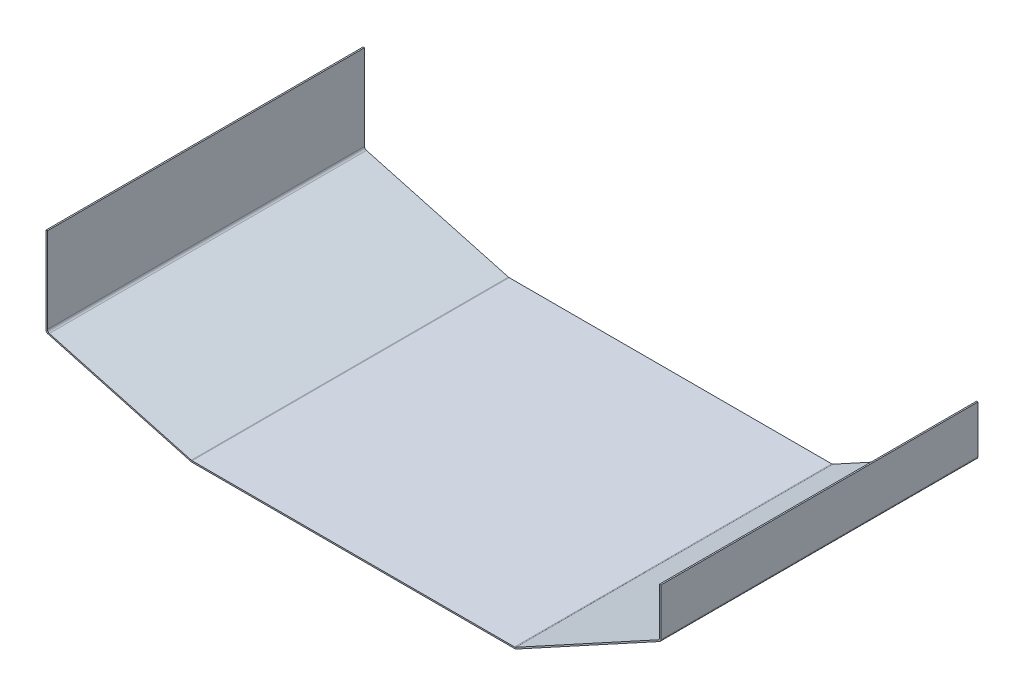
SolidWorks part; units mm, degrees
ref_plane "Front Plane" through (0, 0, 0) normal (0, 0, 1) x (1, 0, 0)
ref_plane "Top Plane" through (0, 0, 0) normal (0, 1, 0) x (1, 0, 0)
ref_plane "Right Plane" through (0, 0, 0) normal (1, 0, 0) x (0, 0, -1)
sketch "Sketch1" plane through (0, 0, 0) normal (0, 0, 1) x (1, 0, 0)
  line L0 (0, 0) -> (0, -100)
  line L1 (0, -100) -> (165, -145)
  line L2 (165, -145) -> (535, -145)
  line L3 (535, -145) -> (700, -55)
  line L4 (700, -55) -> (700, 0)
  line L5 (0, 0) -> (700, 0) construction
  dimension "D1" = 145
  dimension "D2" = 165
  dimension "D3" = 700
  dimension "D4" = 100
  dimension "D5" = 165
  dimension "D6" = 55
extrude "Extrude-Thin1" add sketch "Sketch1" along normal up to surface (362.7 mm away) thin thin type one direction wall 1.5875
fillet "Fillet1" radius 3 8 edges at (700, -55, 181.35) (701.5875, -55.9424, 181.35) (535.4048, -146.5875, 181.35) (535, -145, 181.35) (165, -145, 181.35) (164.7874, -146.5875, 181.35) (-1.5875, -101.2125, 181.35) (0, -100, 181.35)
